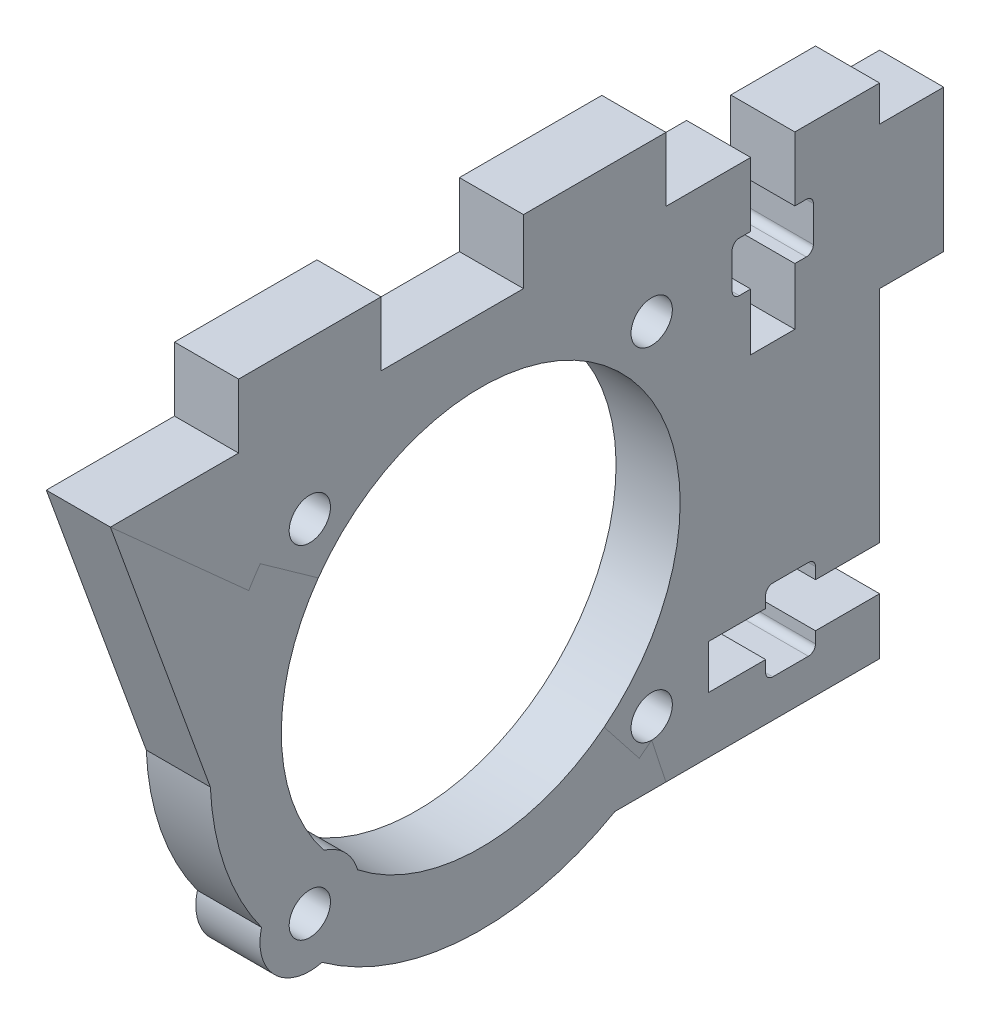
SolidWorks part; units mm, degrees
ref_plane "Front Plane" through (0, 0, 0) normal (0, 0, 1) x (1, 0, 0)
ref_plane "Top Plane" through (0, 0, 0) normal (0, 1, 0) x (1, 0, 0)
ref_plane "Right Plane" through (0, 0, 0) normal (1, 0, 0) x (0, 0, -1)
sketch "Sketch1" plane through (0, 0, 0) normal (1, 0, 0) x (0, 0, -1)
  line L0 (0, 0) -> (0, -35)
  line L1 (0, -35) -> (-54, 0)
  line L2 (-54, 0) -> (0, 0)
  dimension "D1" = 35
  dimension "D2" = 54
extrude "Boss-Extrude1" add sketch "Sketch1" along normal blind 4.5
sketch "Sketch2" plane through (4.5, 0, 0) normal (1, 0, 0) x (0, 0, -1)
  line L0 (0, -35) -> (0, 0) construction
  line L1 (-4.5, -2.5) -> (4.5, -2.5)
  line L2 (-4.5, -2.5) -> (-4.5, -12.5)
  line L3 (-4.5, -12.5) -> (4.5, -12.5)
  line L4 (4.5, -2.5) -> (4.5, -12.5)
  line L5 (-4.5, -2.5) -> (4.5, -12.5) construction
  line L6 (-4.5, -12.5) -> (4.5, -2.5) construction
  line L7 (0, 0) -> (-54, 0) construction
  point P0 (0, -7.5)
  dimension "D1" = 10
  dimension "D2" = 7.5
  dimension "D3" = 4.5
extrude "Boss-Extrude2" add sketch "Sketch2" against normal through all
sketch "Sketch3" plane through (4.5, 0, 0) normal (1, 0, 0) x (0, 0, -1)
  line L0 (0, -35) -> (-15, -35)
  line L1 (0, -25) -> (-54, 0)
  line L4 (0, -35) -> (0, -12.5) construction
  line L5 (0, -25) -> (0, -35)
  line L6 (-54, 0) -> (-15, -35)
  dimension "D1" = 15
  dimension "D2" = 10
extrude "Boss-Extrude3" add sketch "Sketch3" against normal through all
sketch "Sketch4" plane through (4.5, 0, 0) normal (1, 0, 0) x (0, 0, -1)
  line L0 (0, -29.5) -> (-12, -29.5) construction
  line L1 (0, -35) -> (0, -12.5) construction
  line L2 (0, -27.95) -> (-12, -27.95) construction
  line L3 (-12, -27.95) -> (-12, -31.05) construction
  line L4 (0, -31.05) -> (0, -27.95)
  line L5 (0, -27.95) -> (-4.5, -27.95)
  line L6 (-4.5, -27.95) -> (-4.5, -27.15)
  line L7 (-5, -26.65) -> (-7.5, -26.65)
  line L8 (-8, -27.15) -> (-8, -27.95)
  line L9 (-8, -27.95) -> (-12, -27.95)
  line L10 (-12, -27.95) -> (-12, -31.05)
  line L12 (0, -31.05) -> (-12, -31.05) construction
  line L13 (-8, -31.05) -> (-12, -31.05)
  line L14 (-8, -31.85) -> (-8, -31.05)
  line L15 (-5, -32.35) -> (-7.5, -32.35)
  line L16 (-4.5, -31.05) -> (-4.5, -31.85)
  line L17 (0, -31.05) -> (-4.5, -31.05)
  line L18 (4.5, -12.5) -> (4.5, -2.5) construction
  line L19 (0, -18.5) -> (-33.3857, -18.5) construction
  line L20 (-54, 0) -> (-15, -35) construction
  line L37 (0, -31.05) -> (-12, -31.05) construction
  arc A0 (-8, -31.85) -> (-7.5, -32.35) centre (-7.5, -31.85) ccw
  arc A1 (-5, -32.35) -> (-4.5, -31.85) centre (-5, -31.85) ccw
  arc A2 (-4.5, -27.15) -> (-5, -26.65) centre (-5, -27.15) ccw
  arc A3 (-7.5, -26.65) -> (-8, -27.15) centre (-7.5, -27.15) ccw
  point P10 (4.5, -7.5)
  point P20 (-8, -32.35)
  point P23 (-4.5, -32.35)
  point P26 (-4.5, -26.65)
  point P29 (-8, -26.65)
  dimension "D7" = 0.5
  dimension "D1" = 12
  dimension "D2" = 1.55
  dimension "D3" = 2.85
  dimension "D4" = 3.5
  dimension "D5" = 8
  dimension "D6" = 22
extrude "Cut-Extrude1" cut sketch "Sketch4" against normal through all
sketch "Sketch5" plane through (4.5, 0, 0) normal (1, 0, 0) x (0, 0, -1)
  line L0 (0, 0) -> (-54, 0) construction
  line L1 (-25, 4.5) -> (-15, 4.5)
  line L2 (-25, 4.5) -> (-25, 0)
  line L3 (0, 0) -> (-54, 0) construction
  line L4 (-15, 4.5) -> (-15, 0)
  line L5 (-25, 4.5) -> (-20, 0) construction
  line L6 (-20, 0) -> (-15, 4.5) construction
  line L7 (-30, 0) -> (-30, 4.5) construction
  line L8 (-40, 0) -> (-45, 4.5) construction
  line L9 (-35, 4.5) -> (-40, 0) construction
  line L10 (-45, 4.5) -> (-45, 0)
  line L12 (-35, 4.5) -> (-35, 0)
  line L13 (-35, 4.5) -> (-45, 4.5)
  line L14 (-20, 0) -> (-15, 4.5) construction
  line L15 (-15, 0) -> (-25, 0)
  line L16 (-35, 0) -> (-45, 0)
  point P0 (-20, 0)
  point P14 (-40, 0)
  dimension "D3" = 4.5
  dimension "D1" = 20
  dimension "D2" = 10
  dimension "D4" = 20
  dimension "D5" = 5
extrude "Boss-Extrude4" add sketch "Sketch5" against normal through all
sketch "Sketch8" [suppressed] plane through (4.5, 0, 0) normal (1, 0, 0) x (0, 0, -1)
  line L0 (-15, -30) -> (-27, -30) construction
  line L1 (-15, -35) -> (-27, -35)
  line L2 (-15, -25) -> (-27, -25)
  line L3 (-15, -35) -> (0, -35) construction
  line L4 (-15, -25) -> (-15, -35)
  arc A1 (-27, -25) -> (-27, -35) centre (-27, -30) ccw
  dimension "D5" = 5
  dimension "D1" = 0
  dimension "D2" = 12
  dimension "D3" = 0
  dimension "D4" = 10
extrude "Boss-Extrude5" [suppressed] add sketch "Sketch8" against normal up to surface (4.5 mm away) up to face at (0, -17.3125, 11.9375)
sketch "Sketch9" [suppressed] plane through (4.5, 0, 0) normal (1, 0, 0) x (0, 0, -1)
  line L0 (-27, -30) -> (-22, -30) construction
  line L1 (-27, -27) -> (-22, -27)
  line L2 (-27, -33) -> (-22, -33)
  arc A0 (-27, -27) -> (-27, -33) centre (-27, -30) ccw
  arc A1 (-22, -33) -> (-22, -27) centre (-22, -30) ccw
  point P3 (-24.5, -30)
  dimension "D1" = 3
  dimension "D2" = 5
extrude "Cut-Extrude3" [suppressed] cut sketch "Sketch9" against normal through all
sketch "Sketch10" plane through (0, 0, 0) normal (-1, 0, 0) x (0, 0, 1)
  line L0 (15, -35) -> (54, -12)
  line L1 (54, -12) -> (54, 0)
  line L3 (54, 0) -> (15, -35)
  dimension "D1" = 12
extrude "Boss-Extrude6" [suppressed] add sketch "Sketch10" against normal through all
sketch "Sketch6" plane through (4.5, 0, 0) normal (1, 0, 0) x (0, 0, -1)
  line L0 (-30, 0) -> (-30, -11) construction
  line L1 (-25, 0) -> (-35, 0) construction
  line L2 (-28.45, -11) -> (-31.55, -11) construction
  line L3 (-31.55, -11) -> (-31.55, 0) construction
  line L4 (-28.45, 0) -> (-31.55, 0)
  line L5 (-31.55, 0) -> (-31.55, -4.5)
  line L6 (-31.55, -4.5) -> (-32.35, -4.5)
  line L7 (-32.85, -5) -> (-32.85, -7.5)
  line L8 (-32.35, -8) -> (-31.55, -8)
  line L9 (-31.55, -8) -> (-31.55, -11)
  line L10 (-31.55, -11) -> (-28.45, -11)
  line L11 (-28.45, -11) -> (-28.45, 0) construction
  line L12 (-28.45, -8) -> (-28.45, -11)
  line L13 (-27.65, -8) -> (-28.45, -8)
  line L14 (-27.15, -5) -> (-27.15, -7.5)
  line L15 (-28.45, -4.5) -> (-27.65, -4.5)
  line L16 (-28.45, 0) -> (-28.45, -4.5)
  arc A0 (-32.85, -7.5) -> (-32.35, -8) centre (-32.35, -7.5) ccw
  arc A1 (-32.35, -4.5) -> (-32.85, -5) centre (-32.35, -5) ccw
  arc A2 (-27.65, -4.5) -> (-27.15, -5) centre (-27.65, -5) cw
  arc A3 (-27.15, -7.5) -> (-27.65, -8) centre (-27.65, -7.5) cw
  point P12 (-32.85, -8)
  point P15 (-32.85, -4.5)
  point P26 (-27.15, -4.5)
  point P27 (-27.15, -8)
  dimension "D2" = 1.55
  dimension "D4" = 3.5
  dimension "D6" = 0.5
  dimension "D1" = 11
  dimension "D3" = 8
  dimension "D5" = 2.85
extrude "Cut-Extrude2" [suppressed] cut sketch "Sketch6" against normal through all
sketch "Sketch11" plane through (0, 0, 0) normal (-1, 0, 0) x (0, 0, 1)
  line L0 (7.5, 0) -> (7.5, -12) construction
  line L1 (0, 0) -> (15, 0) construction
  line L2 (5.95, -12) -> (9.05, -12)
  line L3 (9.05, -12) -> (9.05, -8)
  line L4 (9.05, -8) -> (9.85, -8)
  line L5 (10.35, -7.5) -> (10.35, -5)
  line L6 (9.85, -4.5) -> (9.05, -4.5)
  line L7 (9.05, -4.5) -> (9.05, 0)
  line L8 (9.05, 0) -> (5.95, 0)
  line L9 (9.05, -8) -> (9.05, -4.5) construction
  line L10 (0, 0) -> (15, 0) construction
  line L11 (5.95, -8) -> (5.95, -4.5) construction
  line L12 (5.95, -4.5) -> (5.95, 0)
  line L13 (5.15, -4.5) -> (5.95, -4.5)
  line L14 (4.65, -7.5) -> (4.65, -5)
  line L15 (5.95, -8) -> (5.15, -8)
  line L16 (5.95, -12) -> (5.95, -8)
  arc A0 (10.35, -5) -> (9.85, -4.5) centre (9.85, -5) ccw
  arc A1 (5.15, -4.5) -> (4.65, -5) centre (5.15, -5) ccw
  arc A2 (9.85, -8) -> (10.35, -7.5) centre (9.85, -7.5) ccw
  arc A3 (4.65, -7.5) -> (5.15, -8) centre (5.15, -7.5) ccw
  point P11 (7.5, 0)
  point P22 (10.35, -4.5)
  point P25 (4.65, -4.5)
  point P28 (10.35, -8)
  point P31 (4.65, -8)
  dimension "D7" = 0.5
  dimension "D1" = 12
  dimension "D3" = 2.85
  dimension "D8" = 0.5
  dimension "D2" = 3.5
  dimension "D4" = 8
  dimension "D5" = 1.55
  dimension "D6" = 0
extrude "Cut-Extrude4" cut sketch "Sketch11" against normal through all
sketch "Sketch12" plane through (0, 0, 0) normal (-1, 0, 0) x (0, 0, 1)
  line L0 (28, -18.5) -> (16, -6.5) construction
  line L1 (28, -18.5) -> (28, -4.5) construction
  line L2 (28, -18.5) -> (40, -6.5) construction
  line L3 (28, -18.5) -> (14, -18.5) construction
  line L4 (28, -18.5) -> (16, -30.5) construction
  line L5 (28, -18.5) -> (16, -6.5) construction
  line L6 (0, -27.95) -> (0, -12.5) construction
  line L7 (25, 0) -> (35, 0) construction
  circle A0 centre (28, -18.5) radius 14
  circle A1 centre (16, -6.5) radius 1.45
  circle A2 centre (40, -6.5) radius 1.45
  circle A3 centre (16, -30.5) radius 1.45
  dimension "D1" = 28
  dimension "D2" = 2.9
  dimension "D3" = 12
  dimension "D4" = 45
  dimension "D5" = 28
  dimension "D6" = 18.5
extrude "FanCutout" cut sketch "Sketch12" against normal through all
sketch "Sketch13" plane through (0, 0, 0) normal (-1, 0, 0) x (0, 0, 1)
  line L0 (39.4071, -10.3834) -> (43.481, -7.4847)
  line L1 (19.3358, -29.4969) -> (16.2414, -33.4243)
  line L6 (28, -18.5) -> (54, 0) construction
  line L7 (28, -18.5) -> (15, -35) construction
  arc A0 (19.3358, -29.4969) -> (39.4071, -10.3834) centre (28, -18.5) ccw
  arc A1 (16.2414, -33.4243) -> (43.481, -7.4847) centre (28, -18.5) ccw
  arc A3 (40.4722, -12.1404) -> (20.333, -30.214) centre (28, -18.5) ccw construction
  dimension "D1" = 5
extrude "Boss-Extrude7" add sketch "Sketch13" against normal through all
sketch "Sketch14" plane through (0, 0, 0) normal (-1, 0, 0) x (0, 0, 1)
  line L0 (28, -4.5) -> (28, -32.5) construction
  line L1 (28, -18.5) -> (40, -30.5) construction
  circle A0 centre (28, -18.5) radius 14 construction
  circle A1 centre (40, -30.5) radius 3.5
  dimension "D2" = 7
  dimension "D1" = 45
  dimension "D3" = 12
extrude "Boss-Extrude8" add sketch "Sketch14" against normal through all
sketch "Sketch15" plane through (0, 0, 0) normal (-1, 0, 0) x (0, 0, 1)
  line L0 (42.4749, -32.9749) -> (28, -18.5) construction
  arc A0 (39.1388, -33.8924) -> (43.3924, -29.6388) centre (40, -30.5) ccw construction
  circle A1 centre (40, -30.5) radius 1.45
  dimension "D1" = 2.9
extrude "Cut-Extrude6" cut sketch "Sketch15" against normal through all
sketch "Sketch16" [suppressed] plane through (4.5, 0, 0) normal (1, 0, 0) x (0, 0, -1)
  line L0 (0, -34.5) -> (-39, -34.5) construction
  line L1 (0, -27.95) -> (0, -12.5) construction
  line L2 (-15, -34.5) -> (-39, -34.5) construction
  line L3 (-15, -38.5) -> (-39, -38.5)
  line L4 (-15, -30.5) -> (-39, -30.5)
  arc A0 (-15, -38.5) -> (-15, -30.5) centre (-15, -34.5) ccw
  arc A1 (-39, -30.5) -> (-39, -38.5) centre (-39, -34.5) ccw
  point P5 (-27, -34.5)
  point P12 (0, -20.225)
  dimension "D1" = 4
  dimension "D2" = 34.5
  dimension "D3" = 39
  dimension "D4" = 15
extrude "Boss-Extrude9" [suppressed] add sketch "Sketch16" against normal through all
sketch "Sketch17" [suppressed] plane through (4.5, 0, 0) normal (1, 0, 0) x (0, 0, -1)
  line L0 (-43, -34.5) -> (0, -34.5) construction
  line L1 (0, -27.75) -> (0, -12.5) construction
  line L2 (-26.5, -34.5) -> (-26.5, -20.0064) construction
  arc A0 (-42.1823, -32.0766) -> (-39, -38.5) centre (-39, -34.5) ccw construction
  circle A1 centre (-39, -34.5) radius 1.55
  circle A2 centre (-14, -34.5) radius 1.55
  dimension "D1" = 2.9
  dimension "D2" = 12.5
extrude "Cut-Extrude7" [suppressed] cut sketch "Sketch17" against normal through all
sketch "Sketch18" [suppressed] plane through (4.5, 0, 0) normal (1, 0, 0) x (0, 0, -1)
  line L0 (-15, -38.5) -> (0, -35)
  line L1 (0, -35) -> (-11.0314, -35)
  line L2 (-11.0314, -35) -> (-15, -38.5)
extrude "Boss-Extrude10" [suppressed] add sketch "Sketch18" against normal through all
sketch "Sketch20" [suppressed] plane through (4.5, 0, 0) normal (1, 0, 0) x (0, 0, -1)
  line L0 (0, -35) -> (0, -31.05) construction
  line L1 (-9, -38) -> (-37.9081, -38)
  line L2 (-40.7232, -36.0371) -> (-54, 0)
  line L3 (-54, 0) -> (-15, -35)
  line L4 (-15, -35) -> (-6, -35)
  line L5 (-9, -38) -> (-6, -35)
  line L6 (-40.7232, -36.0371) -> (-40, -38) construction
  line L7 (-40, -38) -> (-37.9081, -38) construction
  arc A1 (-37.9081, -38) -> (-40.7232, -36.0371) centre (-37.9081, -35) cw
  point P0 (0, -33.025)
  point P14 (-40, -38)
  dimension "D3" = 6
  dimension "D4" = 3
  dimension "D1" = 40
  dimension "D2" = 3
  dimension "D5" = 135
extrude "Boss-Extrude11" [suppressed] add sketch "Sketch20" against normal through all
sketch "Sketch21" [suppressed] plane through (4.5, 0, 0) normal (1, 0, 0) x (0, 0, -1)
  line L0 (0, -34.5) -> (-41.2895, -34.5) construction
  line L1 (0, -35) -> (0, -31.05) construction
  line L2 (-54, 0) -> (-40.7232, -36.0371) construction
  line L3 (0, -27.95) -> (0, -12.5) construction
  circle A0 centre (-36, -34.5) radius 1.45
  circle A1 centre (-11, -34.5) radius 1.45
  dimension "D2" = 2.9
  dimension "D3" = 2.9
  dimension "D1" = 25
  dimension "D4" = 34.5
  dimension "D5" = 11
extrude "Cut-Extrude8" [suppressed] cut sketch "Sketch21" against normal through all
sketch "Sketch22" [suppressed] plane through (4.5, 0, 0) normal (1, 0, 0) x (0, 0, -1)
  line L0 (0, -27.95) -> (0, -12.5) construction
  line L1 (-25, 0) -> (-35, 0) construction
  circle A0 centre (-28, -18) radius 13.25
  dimension "D2" = 18
  dimension "D3" = 26.5
  dimension "D1" = 28
extrude "Cut-Extrude9" [suppressed] cut sketch "Sketch22" against normal through all
sketch "Sketch24" plane through (0, 0, 0) normal (-1, 0, 0) x (0, 0, 1)
  line L0 (15, -35) -> (20, -35)
  line L1 (20, -35) -> (16, -31.95)
  line L2 (16, -31.95) -> (15, -35)
  circle A0 centre (16, -30.5) radius 1.45 construction
  dimension "D1" = 5
extrude "Boss-Extrude13" add sketch "Sketch24" against normal through all
sketch "Sketch25" plane through (0, 0, 0) normal (-1, 0, 0) x (0, 0, 1)
  line L0 (54, 0) -> (46.9826, -19.3121)
  line L1 (46.9826, -19.3121) -> (44.2874, -8.7164)
  line L2 (44.2874, -8.7164) -> (54, 0)
  arc A0 (43.3924, -29.6388) -> (44.2874, -8.7164) centre (28, -18.5) ccw construction
extrude "Boss-Extrude15" add sketch "Sketch25" against normal through all
equation "\"X-ROD-SPACING\"=45"
equation "\"Y-ROD-SPACING\"=75"
equation "\"Z-ROD-SPACING\"=17.5"
equation "\"Y-BED-OFFSET\"=2"
equation "\"Y-BED-ROD-INSET\"=3.5"
equation "\"Y-BED-SCREW-SPACING\"=209"
equation "\"Y-BED-SCREW-CUTOUT-SLOT-HEIGHT\"=2.5"
equation "\"T-SLOT-NUT-FILLET-RADIUS\"=0.5"
equation "\"T-SLOT-SCREW-SHAFT-RADIUS\"=1.55"
equation "\"T-SLOT-SCREW-SHAFT-CUTOUT-LENGTH\"=11"
equation "\"T-SLOT-NUT-DEPTH\"=3.5"
equation "\"T-SLOT-NUT-WIDTH\"=2.85"
equation "\"T-SLOT-NUT-END-DISTANCE\"=8"
equation "\"ACRYLIC-THICKNESS\"=10"
equation "\"ACRYLIC-THICKNESS2\"=4.5"
equation "\"ACRYLIC-TAB-CUTOUT-SIZE\"=\"ACRYLIC-THICKNESS\"+\"ACRYLIC-TAB-TOLERANCE\"*2"
equation "\"ACRYLIC-TAB-WIDTH\"=\"ACRYLIC-THICKNESS\""
equation "\"ACRYLIC-M3-HOLE\"=2.9"
equation "\"SMOOTHROD-CAP-SCREW-DISTANCE\"=20"
equation "\"FRAME-WIDTH-INNER\"=370"
equation "\"NEMA17-HOLE-SPACING\"=31"
equation "\"NEMA17-CENTRAL-CUTOUT\"=22.5"
equation "\"Z-BRACKET-REACH\"=57"
equation "\"Z-ROD-INSET\"=13.5"
equation "\"TOP-BRACKET-SPACING\"=40"
equation "\"SMOOTHROD-X-LENGTH\"=350"
equation "\"SMOOTHROD-Y-LENGTH\"=350"
equation "\"SMOOTHROD-Z-LENGTH\"=350"
equation "\"SMOOTHROD-TIGHTENING-HEADROOM\"=.25"
equation "\"LEADSCREW-Z-LENGTH\"=300"
equation "\"SCREW-LENGTH-FRAME\"=\"ACRYLIC-THICKNESS\" + 10"
equation "\"SCREW-LENGTH-MOTOR\"=\"ACRYLIC-THICKNESS\" + 5"
equation "\"SCREW-LENGTH-EXTRUDER\"=28"
equation "\"SCREW-HEAD-RADIUS\"=6"
equation "\"PRINTED-X-SMOOTHROD-DIAMETER\"=8.8"
equation "\"PRINTED-X-SMOOTHROD-CUTOUT\"=10"
equation "\"PRINTED-X-BASE-HEIGHT\"=10"
equation "\"PRINTED-LM8UU-CUTOUT-SIZE\"=15.5"
equation "\"PRINTED-LM8UU-CUTOUT-LENGTH\"=24.5"
equation "\"PRINTED-X-IDLER-HEIGHT\"=16"
equation "\"PSU-MOUNTING-WIDTH\"=50"
equation "\"PSU-MOUNTING-HEIGHT\"=150"
equation "\"Y-BELT-TO-ROD-DISTANCE\"=20"
equation "\"SPOOL-HOLDER-ROD-SPACING\"=150"
equation "\"ACRYLIC-X-CARRIAGE-WIDTH\"=55"
equation "\"ACRYLIC-X-CARRIAGE-HEIGHT\"=75"
equation "\"ACRYLIC-X-CARRIAGE-SCREW-SPACING-X\"=15"
equation "\"ACRYLIC-X-CARRIAGE-SCREW-SPACING-Y\"=33"
equation "\"ACRYLIC-X-CARRIAGE-CENTER-TAB-SPACING\"=14"
equation "\"ACRYLIC-X-CARRIAGE-EXTRUDER-SHELF-DEPTH\"=\"ACRYLIC-X-CARRIAGE-EXTRUDER-OFFSET\" + 28"
equation "\"D2@Sketch1\"=\"ACRYLIC-X-CARRIAGE-EXTRUDER-SHELF-DEPTH\""
equation "\"D1@Boss-Extrude1\"=\"ACRYLIC-THICKNESS2\""
equation "\"D1@Sketch2\"=\"ACRYLIC-TAB-WIDTH\""
equation "\"D3@Sketch2\"=\"ACRYLIC-THICKNESS2\""
equation "\"ACRYLIC-X-CARRIAGE-LM8UU-CUTOUT-WIDTH\"=24.25"
equation "\"ACRYLIC-X-CARRIAGE-EXTRUDER-BRACE-SPACING\"=23"
equation "\"ACRYLIC-X-CARRIAGE-EXTRUDER-BRACE-HEIGHT\"=35"
equation "\"D1@Sketch1\"=\"ACRYLIC-X-CARRIAGE-EXTRUDER-BRACE-HEIGHT\""
equation "\"D1@Sketch4\"=\"T-SLOT-SCREW-SHAFT-CUTOUT-LENGTH\"+1"
equation "\"D2@Sketch4\"=\"T-SLOT-SCREW-SHAFT-RADIUS\""
equation "\"D3@Sketch4\"=\"T-SLOT-NUT-WIDTH\""
equation "\"D4@Sketch4\"=\"T-SLOT-NUT-DEPTH\""
equation "\"D5@Sketch4\"=\"T-SLOT-NUT-END-DISTANCE\""
equation "\"D7@Sketch4\"=\"T-SLOT-NUT-FILLET-RADIUS\""
equation "\"ACRYLIC-X-CARRIAGE-EXTRUDER-BRACE-SCREW-SPACING\"=22"
equation "\"D6@Sketch4\"=\"ACRYLIC-X-CARRIAGE-EXTRUDER-BRACE-SCREW-SPACING\""
equation "\"ACRYLIC-X-CARRIAGE-EXTRUDER-BRACE-TAB-OFFSET\"=20"
equation "\"D1@Sketch5\"=\"ACRYLIC-X-CARRIAGE-EXTRUDER-BRACE-TAB-OFFSET\""
equation "\"D2@Sketch5\"=\"ACRYLIC-TAB-WIDTH\""
equation "\"D3@Sketch5\"=\"ACRYLIC-THICKNESS2\""
equation "\"ACRYLIC-X-CARRIAGE-EXTRUDER-OFFSET\"=26"
equation "\"ACRYLIC-X-CARRIAGE-EXTRUDER-ANGLE\"=90"
equation "\"D1@Sketch6\"=\"T-SLOT-SCREW-SHAFT-CUTOUT-LENGTH\""
equation "\"D2@Sketch6\"=\"T-SLOT-SCREW-SHAFT-RADIUS\""
equation "\"D3@Sketch6\"=\"T-SLOT-NUT-END-DISTANCE\""
equation "\"D4@Sketch6\"=\"T-SLOT-NUT-DEPTH\""
equation "\"D5@Sketch6\"=\"T-SLOT-NUT-WIDTH\""
equation "\"D6@Sketch6\"=\"T-SLOT-NUT-FILLET-RADIUS\""
equation "\"D1@Sketch11\"=\"T-SLOT-SCREW-SHAFT-CUTOUT-LENGTH\"+1"
equation "\"D2@Sketch11\"=\"T-SLOT-NUT-DEPTH\""
equation "\"D3@Sketch11\"=\"T-SLOT-NUT-WIDTH\""
equation "\"D4@Sketch11\"=\"T-SLOT-NUT-END-DISTANCE\""
equation "\"D5@Sketch11\"=\"T-SLOT-SCREW-SHAFT-RADIUS\""
equation "\"D7@Sketch11\"=\"T-SLOT-NUT-FILLET-RADIUS\""
equation "\"D8@Sketch11\"=\"T-SLOT-NUT-FILLET-RADIUS\""
equation "\"D2@Sketch12\"=\"ACRYLIC-M3-HOLE\""
equation "\"D1@Sketch15\"=\"ACRYLIC-M3-HOLE\""
equation "\"D1@Sketch17\"=\"ACRYLIC-M3-HOLE\""
equation "\"D2@Sketch21\"=\"ACRYLIC-M3-HOLE\""
equation "\"D3@Sketch21\"=\"ACRYLIC-M3-HOLE\""
